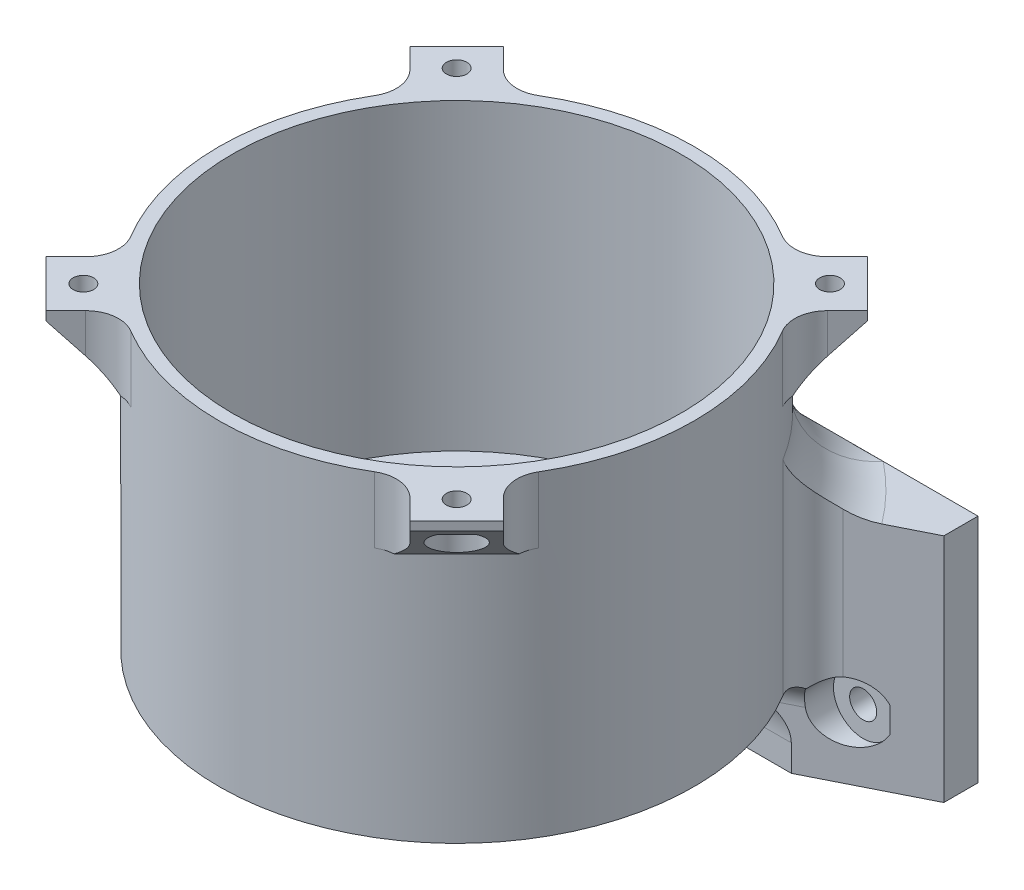
SolidWorks part; units mm, degrees
ref_plane "Front Plane" through (0, 0, 0) normal (0, 0, 1) x (1, 0, 0)
ref_plane "Top Plane" through (0, 0, 0) normal (0, 1, 0) x (1, 0, 0)
ref_plane "Right Plane" through (0, 0, 0) normal (1, 0, 0) x (0, 0, -1)
sketch "Sketch1" plane through (0, 0, 0) normal (0, 1, 0) x (1, 0, 0)
  circle A0 centre (0, 0) radius 36
  dimension "D1" = 72
extrude "Boss-Extrude1" add sketch "Sketch1" against normal blind 48
sketch "Sketch2" plane through (0, -48, 0) normal (0, -1, 0) x (1, 0, 0)
  circle A0 centre (0, 0) radius 15
  dimension "D1" = 30
extrude "Cut-Extrude1" cut sketch "Sketch2" against normal up to next
ref_axis "Axis1" through (-39.6, 0, 0) along (1, 0, 0)
ref_axis "Axis2" through (0, 0, -39.6) along (0, 0, 1)
sketch "Sketch3" plane through (0, 0, 0) normal (0, 1, 0) x (1, 0, 0)
  line L0 (0, 0) -> (-36.7653, -36.7653) construction
  line L1 (-39.6, 0) -> (39.6, 0) construction
  line L2 (-20.5061, -27.5772) -> (-27.5772, -34.6482)
  line L3 (-20.5061, -27.5772) -> (-27.5772, -20.5061)
  line L4 (-27.5772, -34.6482) -> (-34.6482, -27.5772)
  line L5 (-27.5772, -20.5061) -> (-34.6482, -27.5772)
  line L6 (-20.5061, -27.5772) -> (-34.6482, -27.5772) construction
  line L7 (-27.5772, -34.6482) -> (-27.5772, -20.5061) construction
  point P5 (0, 0)
  point P6 (-27.5772, -27.5772)
  point P7 (0, 0)
  dimension "D1" = 45
  dimension "D2" = 10
  dimension "D3" = 44
extrude "Boss-Extrude2" add sketch "Sketch3" against normal blind 10
ref_point "Point1"
ref_axis "Axis3" through (-31.1127, -10, 31.1127) along (0.6895, 0.2216, -0.6895)
hole_wizard "CBORE for M3 Pan Head Machine Screw1" positions "Sketch4" profile "Sketch5" counterbore size "M3" standard "ANSI Metric" end condition up to next
sketch "Sketch4" plane through (0, -10, 0) normal (0, -1, 0) x (-1, 0, 0)
  line L0 (31.1127, -31.1127) -> (0, 0) construction
  line L1 (34.6482, -27.5772) -> (27.5772, -34.6482) construction
  point P0 (28.2843, -28.2843)
  point P7 (0, 0)
  dimension "D1" = 4
sketch "Sketch5" plane through (-28.2843, -10, 28.2843) normal (1, 0, 0) x (0, 0, -1)
  line L0 (0, 0) -> (0, 10)
  line L1 (0, 10) -> (1.55, 10)
  line L3 (1.55, 10) -> (1.55, 7.4)
  line L4 (1.55, 7.4) -> (3.5, 7.4)
  line L5 (3.5, 7.4) -> (3.5, 0)
  line L7 (3.5, 0) -> (0, 0)
  line L11 (0, -6.35) -> (0, 107.95) construction
  dimension "Thru Hole Dia." = 3.1
  dimension "Thru Hole Depth" = 10
  dimension "C'Bore Dia." = 7
  dimension "C'Bore Depth" = 7.4
sketch "Sketch6" plane through (3.5355, 0, 3.5355) normal (0.7071, 0, 0.7071) x (0.7071, 0, -0.7071)
  line L0 (-44, -1.3631) -> (-44, -10)
  line L1 (-44, -10) -> (-44, 0) construction
  line L2 (-44, -10) -> (-36, -10)
  line L3 (-44, -10) -> (-35.6511, -10) construction
  line L4 (-36, -10) -> (-35.6511, -10) construction
  line L5 (-36, -10) -> (-44, -1.3631)
extrude "Cut-Extrude2" cut sketch "Sketch6" against normal up to next
fillet "Fillet1" radius 5 2 edges at (-21.6736, -5, 28.7447) (-28.7447, -5, 21.6736)
pattern_circular "CirPattern1" count 4 every 90 about axis through (0, 0.001, 0) along (0, -1, 0) of "Cut-Extrude2", "CBORE for M3 Pan Head Machine Screw1", "Boss-Extrude2", "Fillet1"
ref_plane "Plane1" through (0, -62, 0) normal (0, -1, 0) x (-1, 0, 0)
sketch "Sketch13" plane through (0, -62, 0) normal (0, -1, 0) x (-1, 0, 0)
  line L0 (0, 39.6) -> (0, -39.6) construction
  line L1 (-43, 23.1) -> (43, 23.1)
  line L2 (-43, 23.1) -> (-43, 36)
  line L3 (-43, 36) -> (43, 36)
  line L4 (43, 23.1) -> (43, 36)
  line L5 (-43, 23.1) -> (43, 36) construction
  line L6 (-43, 36) -> (43, 23.1) construction
  circle A0 centre (0, 0) radius 36 construction
  point P0 (0, 29.55)
  dimension "D1" = 12.9
  dimension "D2" = 86
extrude "Boss-Extrude4" add sketch "Sketch13" against normal blind 35
sketch "Sketch11" plane through (0, 0, 0) normal (0, 1, 0) x (1, 0, 0)
  circle A0 centre (0, 0) radius 34
  dimension "D1" = 68
extrude "Cut-Extrude4" cut sketch "Sketch11" against normal offset from surface (46 mm away) 2 up to face at (0, -48, -15)
hole_wizard "CBORE for M4 Pan Head Machine Screw2" positions "Sketch14" profile "Sketch15" counterbore size "M4" standard "ANSI Metric" end condition up to next
sketch "Sketch14" plane through (0, 0, -23.1) normal (0, 0, 1) x (1, 0, 0)
  line L0 (43, -27) -> (43, -62) construction
  line L1 (43, -62) -> (-43, -62) construction
  line L2 (-43, -27) -> (-43, -62) construction
  point P0 (33.5, -52.5)
  point P8 (-33.5, -52.5)
  dimension "D1" = 9.5
  dimension "D2" = 9.5
  dimension "D3" = 9.5
sketch "Sketch15" plane through (33.5, -52.5, -23.1) normal (1, 0, 0) x (0, -1, 0)
  line L0 (0, 0) -> (0, 12.9)
  line L1 (0, 12.9) -> (2.05, 12.9)
  line L3 (2.05, 12.9) -> (2.05, 5)
  line L4 (2.05, 5) -> (4.5, 5)
  line L5 (4.5, 5) -> (4.5, 0)
  line L7 (4.5, 0) -> (0, 0)
  line L11 (0, -6.35) -> (0, 107.95) construction
  dimension "Thru Hole Dia." = 4.1
  dimension "Thru Hole Depth" = 12.9
  dimension "C'Bore Dia." = 9
  dimension "C'Bore Depth" = 5
sketch "Sketch16" plane through (0, -62, 0) normal (0, -1, 0) x (1, 0, 0)
  line L0 (-27.6114, -23.1) -> (-43, -30.8209)
  line L1 (-43, -23.1) -> (-43, -36) construction
  line L2 (-43, -30.8209) -> (-43, -23.1)
  line L3 (-43, -23.1) -> (-27.6114, -23.1)
extrude "Cut-Extrude5" cut sketch "Sketch16" against normal up to next
mirror "Mirror2" about plane through (0, 0, 0) normal (1, 0, 0) of "Cut-Extrude5"
fillet "Fillet3" radius 5 2 edges at (-27.6114, -37.5, -23.1) (27.6114, -37.5, -23.1)
fillet "Fillet2" radius 10 3 edges at (-17.6694, -27, -31.3654) (17.6694, -27, -31.3654) (0, -48, -23.1)
fillet "Fillet4" radius 5 2 edges at (-20.252, -48, -19.4075) (20.252, -48, -19.4075)
ref_axis "Axis4" through (0, -48, 0) along (0, 1, 0)
